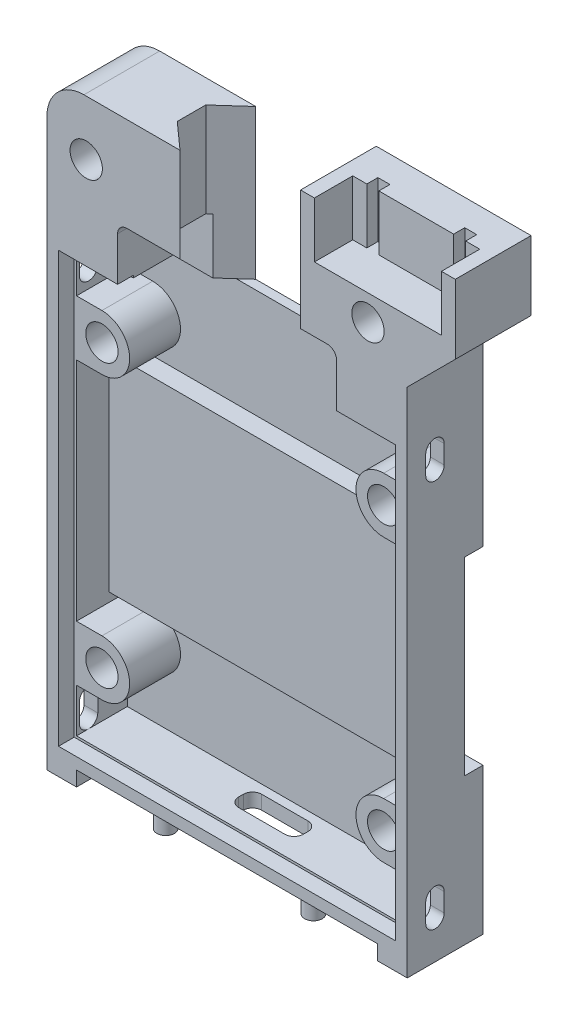
SolidWorks part; units mm, degrees
ref_plane "Front Plane" through (0, 0, 0) normal (0, 0, 1) x (1, 0, 0)
ref_plane "Top Plane" through (0, 0, 0) normal (0, 1, 0) x (1, 0, 0)
ref_plane "Right Plane" through (0, 0, 0) normal (1, 0, 0) x (0, 0, -1)
sketch "Sketch1" plane through (0, 0, 0) normal (0, 0, 1) x (1, 0, 0)
  line L0 (15.25, -20.35) -> (18, -20.35)
  line L1 (-19.5, -32.6) -> (19.5, -32.6)
  line L2 (-19.5, -32.6) -> (-19.5, 31.1)
  line L3 (-19.5, 31.1) -> (19.5, 31.1)
  line L4 (19.5, -32.6) -> (19.5, 31.1)
  line L5 (-15.25, -20.35) -> (-18, -20.35)
  line L6 (15.25, -26.35) -> (18, -26.35)
  line L7 (6.95, 31.1) -> (-15.5, 31.1) construction
  line L8 (-18, -31.1) -> (-18, 29.6)
  line L9 (-18, 29.6) -> (18, 29.6)
  line L10 (18, -31.1) -> (18, 29.6)
  line L11 (-18, -31.1) -> (18, -31.1)
  line L12 (-18, 14.9) -> (18, 14.9)
  line L13 (7.85, 14.9) -> (-4.95, 14.9) construction
  line L14 (-15.25, 4.15) -> (-18, 4.15)
  line L15 (-15.25, 10.15) -> (-18, 10.15)
  line L16 (15.25, 10.15) -> (18, 10.15)
  line L17 (15.25, 4.15) -> (18, 4.15)
  line L18 (-15.25, -26.35) -> (-18, -26.35)
  line L19 (19.5, -34.2) -> (19.5, -18.35) construction
  line L20 (-19.5, -34.2) -> (-19.5, -18.35) construction
  line L21 (15.3, -32.6) -> (-15.3, -32.6) construction
  line L22 (0, 31.1) -> (0, -32.6) construction
  line L23 (9.45, 26.9) -> (24.7, 26.9)
  line L24 (9.45, 26.9) -> (9.45, 33.9)
  line L25 (9.45, 33.9) -> (24.7, 33.9)
  line L26 (24.7, 26.9) -> (24.7, 33.9)
  line L27 (18, 29.6) -> (19.5, 31.1) construction
  line L28 (18.75, 30.35) -> (0, 30.35) construction
  line L29 (9.45, 26.9) -> (7.95, 26.9) construction
  line L30 (-7.95, 31.1) -> (7.95, 31.1)
  line L31 (-7.95, 31.1) -> (-7.95, 29.6)
  line L32 (-7.95, 29.6) -> (7.95, 29.6)
  line L33 (7.95, 31.1) -> (7.95, 29.6)
  line L34 (-7.95, 31.1) -> (7.95, 29.6) construction
  line L35 (-7.95, 29.6) -> (7.95, 31.1) construction
  line L36 (7.95, 26.9) -> (7.95, 29.6) construction
  line L37 (18, 29.6) -> (19.5, 29.6) construction
  line L38 (24.7, 26.4) -> (19.5, 21.2)
  line L39 (9.45, 33.9) -> (7.95, 33.9)
  line L40 (23.2, 33.9) -> (23.2, 26.9)
  line L41 (7.95, 33.9) -> (7.95, 31.1)
  line L42 (24.7, 30.4) -> (23.2, 30.4) construction
  line L43 (24.7, 26.9) -> (19.5, 26.9)
  line L44 (24.7, 26.9) -> (24.7, 26.4)
  line L45 (24.7, 26.4) -> (19.5, 26.4)
  line L46 (19.5, 26.9) -> (19.5, 26.4)
  circle A0 centre (15.25, -23.35) radius 1.75
  arc A1 (-15.5, 31.1) -> (-19.5, 27.1) centre (-15.5, 27.1) ccw construction
  circle A2 centre (15.25, -23.35) radius 3
  arc A3 (-15.5, 31.1) -> (-19.5, 27.1) centre (-15.5, 27.1) ccw
  arc A4 (-15.5, 29.6) -> (-18, 27.1) centre (-15.5, 27.1) ccw
  circle A6 centre (-15.25, -23.35) radius 1.75
  circle A7 centre (-15.25, -23.35) radius 1.75
  circle A8 centre (-15.25, 7.15) radius 1.75
  circle A9 centre (15.25, 7.15) radius 1.75
  circle A10 centre (15.25, 25.15) radius 1.75
  circle A11 centre (-15.25, 25.15) radius 1.75
  circle A12 centre (-15.25, -23.35) radius 3
  circle A13 centre (-15.25, -23.35) radius 3
  circle A14 centre (15.25, 7.15) radius 3
  circle A15 centre (-15.25, 7.15) radius 3
  dimension "D2" = 1.5
  dimension "D4" = 6
  dimension "D3" = 3.5
  dimension "D5" = 13.75
  dimension "D6" = 15.9
  dimension "D7" = 7
  dimension "D8" = 45
  dimension "D9" = 0.5
  dimension "D1" = 1.5
extrude "Base shape" add sketch "Sketch1" along normal up to surface (8.2 mm away) contours A15 L8 L9 L31 L3 A3 L2 L1 L4 L23 L10 A14 A2 L11 A12 | A12 L8 L18 | A12 L8 A6 | L8 A12 | A12 L5 L8 | A15 L8 L14 | A15 L8 A8 | L8 A15 | A15 L15 L8 | L23 A10 L24 L9 A4 L8 L12 L10 A11 | A4 L9 L8 | L33 L3 L31 L9 | L3 L33 L9 L24 | L24 L9 L10 L23 L4 L3 | L24 L23 L10 L9 | A14 L10 L16 | L10 A14 A9 | A14 L17 L10 | L10 A14 | L10 A2 L6 | A2 L10 A0 | L0 A2 L10 | A2 L10 | L40 L25 L24 L3 L4 L23 | L25 L40 L23 L26 | L38 L45 L4 | L45 L44 L23 L4 | L39 L41 L3 L24 region at (16.8481, -20.9099, 0) region at (17.3601, -20.8437, 0) region at (18.7469, -8.1, 0) region at (17.3601, -25.8563, 0) region at (18.1004, -23.35, 0) region at (17.3601, 4.6437, 0) region at (16.8481, 4.7099, 0) region at (18.1004, 7.15, 0) region at (17.3601, 9.6563, 0) region at (-17.3601, -25.8563, 0) region at (-0.6044, 21.831, 0) region at (-18.1004, -23.35, 0) region at (-17.9169, -23.35, 0) region at (13.725, 28.25, 0) region at (15.3803, 29.9053, 0) region at (-17.3601, -20.8437, 0) region at (22.1, 26.65, 0) region at (17.77, 31.4935, 0) region at (-17.3601, 9.6563, 0) region at (-17.4416, 29.0416, 0) region at (8.7, 30.35, 0) region at (21.2333, 24.6667, 0) region at (23.95, 30.4, 0) region at (-16.8481, 9.5901, 0) region at (-18.1004, 7.15, 0) region at (-17.3601, 4.6437, 0) region at (0, 30.35, 0) region at (8.7, 32.5, 0)
sketch "Sketch3" plane through (19.5, 0, 0) normal (1, 0, 0) x (0, 0, -1)
  line L1 (0, -18.35) -> (-2, -18.35)
  line L2 (0, -18.35) -> (0, 2.15)
  line L3 (0, 2.15) -> (-2, 2.15)
  line L4 (-2, -18.35) -> (-2, 2.15)
  line L5 (0, -18.35) -> (1.75, -18.35) construction
  line L6 (0, 2.15) -> (1.75, 2.15) construction
  line L7 (0, -32.6) -> (0, 21.2) construction
  dimension "D1" = 2
extrude "Strap cut" cut sketch "Sketch3" against normal through all
sketch "Sketch4" plane through (0, 31.1, 0) normal (0, 1, 0) x (1, 0, 0)
  line L2 (7.95, 0) -> (-5.0998, 0)
  line L4 (-15.5, 0) -> (7.95, 0) construction
  line L5 (-15.5, -8.2) -> (7.95, -8.2) construction
  line L6 (7.95, -8.2) -> (-5.0998, -8.2)
  line L12 (7.95, -8.3) -> (7.95, 0.1)
  line L13 (7.95, 0.1) -> (-4.9883, 0.1)
  line L14 (-4.9883, 0.1) -> (-7.95, -2.5553)
  line L15 (-7.95, -2.5553) -> (-7.95, -5.6447)
  line L16 (-7.95, -5.6447) -> (-4.9883, -8.3)
  line L17 (-4.9883, -8.3) -> (7.95, -8.3)
  line L18 (7.95, -8.3) -> (7.95, 0.1)
  line L19 (7.95, 0.1) -> (-4.9883, 0.1)
  line L20 (-4.9883, 0.1) -> (-7.95, -2.5553)
  line L21 (-7.95, -2.5553) -> (-7.95, -5.6447)
  line L22 (-7.95, -5.6447) -> (-4.9883, -8.3)
  line L23 (-4.9883, -8.3) -> (7.95, -8.3)
  dimension "D1" = 0.1
extrude "XT60 cut" cut sketch "Sketch4" against normal up to next contours L21 L22 L18 L20 region at (0.4142, 31.1, 4.1)
sketch "Sketch5" plane through (19.5, 0, 0) normal (1, 0, 0) x (0, 0, -1)
  line L1 (-8.2, -32.6) -> (-8.2, 21.2) construction
  line L2 (-6.2, -31.1) -> (-4.2, -31.1)
  line L3 (-6.2, -31.1) -> (-6.2, -27.1)
  line L4 (-6.2, -27.1) -> (-4.2, -27.1)
  line L5 (-4.2, -31.1) -> (-4.2, -27.1)
  line L6 (-8.2, -31.1) -> (0, -31.1) construction
  line L7 (-8.2, 14.9) -> (0, 14.9) construction
  line L8 (-6.2, 14.9) -> (-4.2, 14.9)
  line L9 (-6.2, 14.9) -> (-6.2, 10.9)
  line L10 (-6.2, 10.9) -> (-4.2, 10.9)
  line L11 (-4.2, 14.9) -> (-4.2, 10.9)
  line L14 (-5.2, -27.1) -> (-5.2, -31.1) construction
  line L15 (-5.2, 14.9) -> (-5.2, 10.9) construction
  circle A0 centre (-5.2, -28.1) radius 1
  circle A1 centre (-5.2, -30.1) radius 1
  circle A2 centre (-5.2, 13.9) radius 1
  circle A3 centre (-5.2, 11.9) radius 1
  point P20 (-5.2, -29.1)
  point P31 (-5.2, 12.9)
  dimension "D3" = 4
  dimension "D1" = 2
  dimension "D2" = 2
extrude "Power wires cut" cut sketch "Sketch5" against normal through all contours A2 | A3 | A3 A2 L9 | A3 L11 A2 | A1 | A0 | A1 L5 A0 | A1 A0 L3 region at (19.5, -30.1, 5.2) region at (19.5, -29.1, 5.9766) region at (19.5, -29.1, 4.4234) region at (19.5, -28.1, 5.2) region at (19.5, 13.9, 5.2) region at (19.5, 12.9, 5.9766) region at (19.5, 12.9, 4.4234) region at (19.5, 11.9, 5.2)
sketch "Sketch6" plane through (0, 0, 8.2) normal (0, 0, 1) x (1, 0, 0)
  line L0 (9.15, 14.9) -> (10.85, 14.9) construction
  line L1 (-11.85, 19.9) -> (11.85, 19.9)
  line L2 (-11.85, 19.9) -> (-11.85, 14.9)
  line L3 (-11.85, 14.9) -> (11.85, 14.9)
  line L4 (11.85, 19.9) -> (11.85, 14.9)
  line L5 (-10.85, 20.9) -> (10.85, 20.9)
  arc A0 (11.85, 19.9) -> (10.85, 20.9) centre (10.85, 19.9) ccw construction
  arc A1 (-10.85, 20.9) -> (-11.85, 19.9) centre (-10.85, 19.9) ccw construction
  arc A2 (11.85, 19.9) -> (10.85, 20.9) centre (10.85, 19.9) ccw
  arc A3 (-10.85, 20.9) -> (-11.85, 19.9) centre (-10.85, 19.9) ccw
  line M1 (7.95, 33.9) -> (7.95, 14.9)
  line M15 (-5.0998, 14.9) -> (-5.0998, 31.1)
  line M118 (7.95, 14.9) -> (18, 14.9)
  line M134 (-18, 14.9) -> (-5.0998, 14.9)
extrude "IO wires cut" cut sketch "Sketch6" against normal blind 6 contours L5 A3 L1 M15 | L1 L2 M134 M15 | L5 L1 M15 M1 | L3 L1 M15 M1 | L1 A2 L5 M1 | L4 L1 M1 M118 region at (-8.3714, 20.3909, 8.2) region at (-8.4749, 17.4, 8.2) region at (1.4251, 20.4, 8.2) region at (1.4251, 17.4, 8.2) region at (9.7995, 20.3839, 8.2) region at (9.9, 17.4, 8.2)
sketch "Sketch7" plane through (-18, 0, 0) normal (1, 0, 0) x (0, 0, -1)
  line L6 (0, -18.35) -> (0, -20.35)
  line L7 (-2, -18.35) -> (0, -18.35)
  line L8 (-2, 2.15) -> (-2, -18.35)
  line L9 (0, 2.15) -> (-2, 2.15)
  line L12 (0, 3.15) -> (-3, 3.15)
  line L13 (-3, 3.15) -> (-3, -19.35)
  line L14 (-3, -19.35) -> (-1, -19.35)
  line L15 (-1, -19.35) -> (-1, -20.35)
  line L16 (-1, -20.35) -> (0, -20.35)
  line L17 (0, 3.15) -> (-1, 3.15)
  line L19 (0, -31.1) -> (-1, -31.1)
  line L22 (0, -31.1) -> (0, -20.35)
  line L23 (0, -20.35) -> (-1, -20.35)
  line L24 (-1, -31.1) -> (-1, -20.35)
  line L25 (0, 3.15) -> (0, 14.9)
  line L26 (0, 14.9) -> (-1, 14.9)
  line L27 (-1, 3.15) -> (-1, 14.9)
  line L28 (-5.2, 14.9) -> (0, 14.9) construction
  line L31 (0, -20.35) -> (0, -18.35) construction
  line L32 (0, 2.15) -> (-2, 2.15) construction
  line M48 (0, -20.35) -> (0, -18.35)
  line M49 (0, -18.35) -> (-2, -18.35)
  line M50 (-2, -18.35) -> (-2, 2.15)
  line M51 (-2, 2.15) -> (0, 2.15)
  line M52 (0, 2.15) -> (0, 4.15)
  line M53 (0, 4.15) -> (-8.2, 4.15)
  line M55 (-8.2, -20.35) -> (0, -20.35)
  dimension "D1" = 1
extrude "Bottom" add sketch "Sketch7" along normal up to surface (36 mm away) contours L27 L25 L26 M53 | L27 L12 M52 M53 | L14 L15 L12 L13 M55 M48 M49 M50 M51 M52 | L24 L19 L22 M55 region at (-18, -8.5273, 2.2091) region at (-18, -25.725, 0.5) region at (-18, 3.65, 0.5) region at (-18, 9.525, 0.5) up to face at (18, -8.1, 2.55)
sketch "Sketch9" plane through (0, 0, 0) normal (0, 0, -1) x (-1, 0, 0)
  circle A0 centre (15.25, -23.35) radius 1.75 construction
  circle A1 centre (-15.25, 7.15) radius 1.75 construction
  circle A2 centre (15.25, 7.15) radius 1.75 construction
  circle A3 centre (15.25, -23.35) radius 1.75 construction
  circle A4 centre (15.25, -23.35) radius 1.75
  circle A5 centre (-15.25, 7.15) radius 1.75
  circle A6 centre (15.25, 7.15) radius 1.75
  circle A7 centre (15.25, -23.35) radius 1.75
  circle A8 centre (-15.25, -23.35) radius 1.75 construction
  circle A9 centre (-15.25, -23.35) radius 1.75
extrude "Bottom holes" cut sketch "Sketch9" against normal up to next contours A5 | A6 | A4 | A9 region at (-15.25, -23.35, 0) region at (15.25, 7.15, 0) region at (-15.25, 7.15, 0) region at (15.25, -23.35, 0)
sketch "Sketch8" plane through (0, 0, 8.2) normal (0, 0, 1) x (1, 0, 0)
  line L0 (-6.2152, 14.9) -> (-18, 14.9) construction
  line L1 (-18.25, 15.15) -> (18.25, 15.15)
  line L2 (-18.25, 15.15) -> (-18.25, -31.35)
  line L3 (-18.25, -31.35) -> (18.25, -31.35)
  line L4 (18.25, 15.15) -> (18.25, -31.35)
  line L5 (-18, 14.9) -> (-18.25, 14.9) construction
  line L6 (-18, 14.9) -> (-18, 15.15) construction
  line L7 (18, 14.9) -> (18.25, 14.9) construction
  line L8 (-18, -31.1) -> (-18, -31.35) construction
  dimension "D1" = 0.25
extrude "PCB cut" cut sketch "Sketch8" against normal blind 1.7
sketch "Sketch11" plane through (0, -32.6, 0) normal (0, -1, 0) x (1, 0, 0)
  line L0 (19.5, 8.2) -> (19.5, 0) construction
  line L1 (-19.5, 8.2) -> (19.5, 8.2)
  line L2 (-19.5, 8.2) -> (-19.5, -1.8)
  line L3 (-19.5, -1.8) -> (19.5, -1.8)
  line L4 (19.5, 8.2) -> (19.5, -1.8)
  line L5 (-19.5, 3.2) -> (19.5, 3.2) construction
  line L6 (0, -1.8) -> (0, 8.2) construction
  line L8 (-2.5, 4.45) -> (2.5, 4.45)
  line L9 (-3.5, 3.45) -> (-3.5, 2.95)
  line L10 (-2.5, 1.95) -> (2.5, 1.95)
  line L11 (3.5, 3.45) -> (3.5, 2.95)
  line L12 (-3.5, 4.45) -> (3.5, 1.95) construction
  line L13 (-3.5, 1.95) -> (3.5, 4.45) construction
  arc A0 (2.5, 4.45) -> (3.5, 3.45) centre (2.5, 3.45) cw
  arc A1 (2.5, 1.95) -> (3.5, 2.95) centre (2.5, 2.95) ccw
  arc A2 (-3.5, 2.95) -> (-2.5, 1.95) centre (-2.5, 2.95) ccw
  arc A3 (-2.5, 4.45) -> (-3.5, 3.45) centre (-2.5, 3.45) ccw
  point P11 (0, 3.2)
  dimension "D4" = 1
  dimension "D1" = 10
  dimension "D2" = 7
  dimension "D3" = 2.5
extrude "Ledbar wires cut" cut sketch "Sketch11" against normal up to next contours L8 A3 L9 A2 L10 A1 L11 A0 region at (0, -32.6, 3.2)
sketch "Sketch13" plane through (0, -32.6, 0) normal (0, -1, 0) x (1, 0, 0)
  line L0 (-19.5, 8.2) -> (19.5, 8.2) construction
  line L1 (19.5, 0) -> (16.3, 0)
  line L2 (19.5, 0) -> (19.5, 8.2)
  line L3 (19.5, 8.2) -> (16.3, 8.2)
  line L4 (16.3, 0) -> (16.3, 8.2)
  line L5 (16.1, -1.8) -> (16.1, 8.2) construction
  line L6 (0, 8.2) -> (0, 0) construction
  line L7 (-19.5, 0) -> (-16.3, 0)
  line L8 (-19.5, 0) -> (-19.5, 8.2)
  line L9 (-19.5, 8.2) -> (-16.3, 8.2)
  line L10 (-16.3, 0) -> (-16.3, 8.2)
  dimension "D1" = 0.2
extrude "Ledbar sides" add sketch "Sketch13" along normal blind 1.6
sketch "Sketch14" plane through (0, -32.6, 0) normal (0, -1, 0) x (1, 0, 0)
  circle A0 centre (8, 6.85) radius 0.95
  circle A1 centre (-8, 6.85) radius 0.95
  dimension "D1" = 1.9
extrude "Ledbar mounts" add sketch "Sketch14" along normal blind 2
sketch "Sketch16" plane through (0, 33.9, 0) normal (0, 1, 0) x (1, 0, 0)
  line L0 (7.95, -6.125) -> (24.7, -6.125) construction
  line L1 (7.95, -8.2) -> (24.7, -8.2) construction
  line L2 (21.675, -2.85) -> (20.375, -2.85)
  line L3 (20.375, -4.05) -> (20.375, -2.85)
  line L4 (9.45, -4.05) -> (23.2, -4.05)
  line L5 (9.45, -4.05) -> (9.45, -8.2)
  line L6 (9.45, -8.2) -> (23.2, -8.2)
  line L7 (23.2, -4.05) -> (23.2, -8.2)
  line L8 (9.45, -4.05) -> (23.2, -8.2) construction
  line L9 (9.45, -8.2) -> (23.2, -4.05) construction
  line L10 (24.7, -8.2) -> (24.7, 0) construction
  line L11 (7.95, -8.2) -> (7.95, 0) construction
  line L12 (16.325, -8.2) -> (16.325, -4.05) construction
  line L13 (11.625, -2.85) -> (11.625, -4.05) construction
  line L14 (10.975, -4.05) -> (12.275, -4.05)
  line L15 (10.975, -4.05) -> (10.975, -2.85)
  line L16 (10.975, -2.85) -> (12.275, -2.85)
  line L17 (12.275, -4.05) -> (12.275, -2.85)
  line L18 (10.975, -2.85) -> (10.975, -8.2) construction
  line L19 (21.675, -4.05) -> (21.675, -2.85)
  point P6 (16.325, -6.125)
  dimension "D1" = 13.75
  dimension "D2" = 4.15
  dimension "D3" = 1.3
  dimension "D4" = 1.2
  dimension "D5" = 4.7
extrude "Balance plug cut" cut sketch "Sketch16" against normal blind 6 contours L7 L4 L5 L6 | L4 L17 L16 L15 | L4 L19 L2 L3 region at (21.025, 33.9, 3.45) region at (16.325, 33.9, 6.125) region at (11.625, 33.9, 3.45)
sketch "Sketch10" [suppressed] plane through (0, 0, 2) normal (0, 0, -1) x (-1, 0, 0)
  line L0 (0, 2.15) -> (0, -18.35) construction
  line L1 (19.5, 2.15) -> (-19.5, 2.15) construction
  line L2 (19.5, -18.35) -> (-19.5, -18.35) construction
  line L3 (19.5, 2.15) -> (19.5, -18.35) construction
  line L4 (-19.5, 1.15) -> (19.5, 1.15)
  line L5 (-19.5, 1.15) -> (-19.5, 0.65)
  line L6 (-19.5, 0.65) -> (19.5, 0.65)
  line L7 (19.5, 1.15) -> (19.5, 0.65)
  line L8 (-19.5, 1.15) -> (19.5, 0.65) construction
  line L9 (-19.5, 0.65) -> (19.5, 1.15) construction
  line L10 (-19.5, 2.15) -> (19.5, 2.15) construction
  line L11 (-19.5, -1.35) -> (19.5, -1.35)
  line L12 (19.5, -0.85) -> (19.5, -1.35)
  line L13 (-19.5, -0.85) -> (19.5, -0.85)
  line L14 (-19.5, -0.85) -> (-19.5, -1.35)
  line L15 (-19.5, -3.35) -> (19.5, -3.35)
  line L16 (19.5, -2.85) -> (19.5, -3.35)
  line L17 (-19.5, -2.85) -> (19.5, -2.85)
  line L18 (-19.5, -2.85) -> (-19.5, -3.35)
  line L19 (-19.5, -5.35) -> (19.5, -5.35)
  line L20 (19.5, -4.85) -> (19.5, -5.35)
  line L21 (-19.5, -4.85) -> (19.5, -4.85)
  line L22 (-19.5, -4.85) -> (-19.5, -5.35)
  line L23 (-19.5, -7.35) -> (19.5, -7.35)
  line L24 (19.5, -6.85) -> (19.5, -7.35)
  line L25 (-19.5, -6.85) -> (19.5, -6.85)
  line L26 (-19.5, -6.85) -> (-19.5, -7.35)
  line L27 (-19.5, -9.35) -> (19.5, -9.35)
  line L28 (19.5, -8.85) -> (19.5, -9.35)
  line L29 (-19.5, -8.85) -> (19.5, -8.85)
  line L30 (-19.5, -8.85) -> (-19.5, -9.35)
  line L31 (-19.5, -11.35) -> (19.5, -11.35)
  line L32 (19.5, -10.85) -> (19.5, -11.35)
  line L33 (-19.5, -10.85) -> (19.5, -10.85)
  line L34 (-19.5, -10.85) -> (-19.5, -11.35)
  line L35 (-19.5, -13.35) -> (19.5, -13.35)
  line L36 (19.5, -12.85) -> (19.5, -13.35)
  line L37 (-19.5, -12.85) -> (19.5, -12.85)
  line L38 (-19.5, -12.85) -> (-19.5, -13.35)
  line L39 (-19.5, -15.35) -> (19.5, -15.35)
  line L40 (19.5, -14.85) -> (19.5, -15.35)
  line L41 (-19.5, -14.85) -> (19.5, -14.85)
  line L42 (-19.5, -14.85) -> (-19.5, -15.35)
  line L43 (-19.5, -17.35) -> (19.5, -17.35)
  line L44 (19.5, -16.85) -> (19.5, -17.35)
  line L45 (-19.5, -16.85) -> (19.5, -16.85)
  line L46 (-19.5, -16.85) -> (-19.5, -17.35)
  point P6 (0, 0.9)
  dimension "D1" = 1
  dimension "D2" = 0.5
  dimension "D4" = 2
  dimension "D3" = 10
extrude "3D print ribs" [suppressed] add sketch "Sketch10" along normal up to surface (2 mm away) up to face at (-17, 7.15, 0)
sketch "Sketch15" [suppressed] plane through (0, 0, 0) normal (0, 0, -1) x (-1, 0, 0)
  line L0 (-8, -34.6) -> (-8, -32.6) construction
  line L1 (-8.95, -34.6) -> (-7.05, -34.6) construction
  line L2 (-8.95, -32.6) -> (-7.05, -32.6) construction
  line L3 (0, -32.6) -> (0, 14.9) construction
  line L4 (-8.25, -34.6) -> (-7.75, -34.6)
  line L5 (-8.25, -34.6) -> (-8.25, -32.6)
  line L6 (-8.25, -32.6) -> (-7.75, -32.6)
  line L7 (-7.75, -34.6) -> (-7.75, -32.6)
  line L8 (-8.25, -34.6) -> (-7.75, -32.6) construction
  line L9 (-8.25, -32.6) -> (-7.75, -34.6) construction
  line L10 (16.3, -32.6) -> (-16.3, -32.6) construction
  line L11 (-7.95, 14.9) -> (5.0998, 14.9) construction
  line L12 (8.25, -32.6) -> (7.75, -32.6)
  line L13 (7.75, -34.6) -> (7.75, -32.6)
  line L14 (8.25, -34.6) -> (7.75, -34.6)
  line L15 (8.25, -34.6) -> (8.25, -32.6)
  point P6 (-8, -33.6)
  dimension "D1" = 0.5
extrude "3D print led supports" [suppressed] add sketch "Sketch15" against normal up to next
